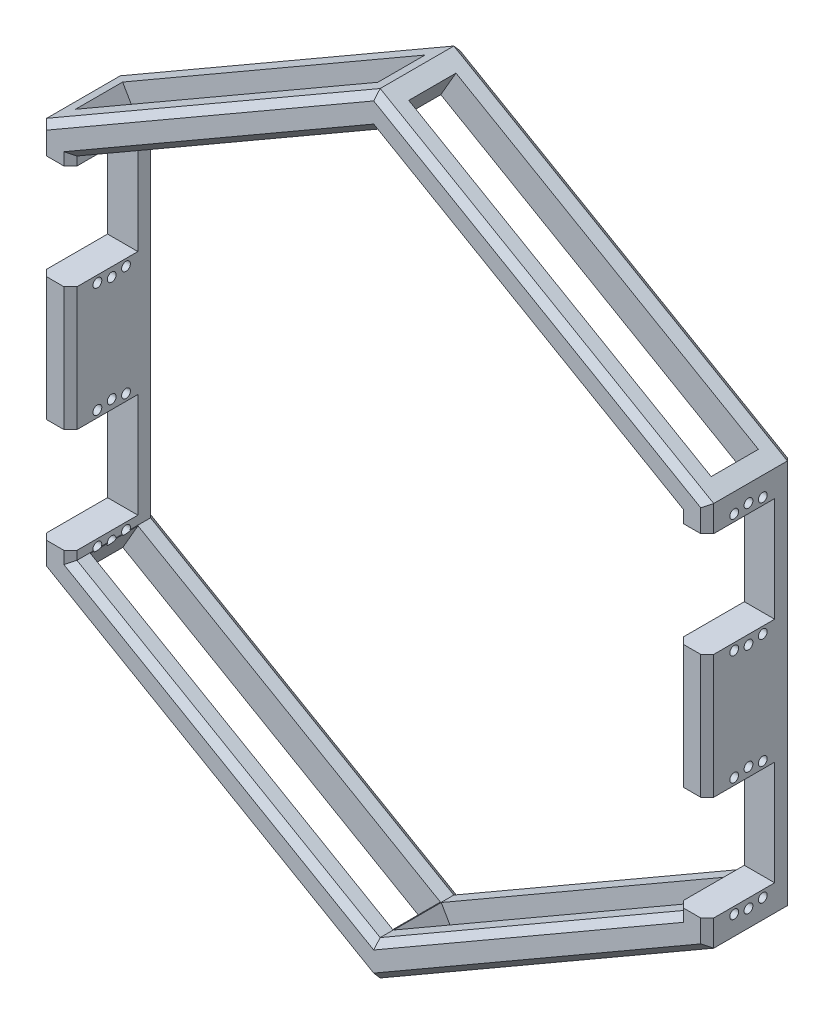
SolidWorks part; units mm, degrees
material "Caoutchouc"
ref_plane "Plan de face" through (0, 0, 0) normal (0, 0, 1) x (1, 0, 0)
ref_plane "Plan de dessus" through (0, 0, 0) normal (0, 1, 0) x (1, 0, 0)
ref_plane "Plan de droite" through (0, 0, 0) normal (1, 0, 0) x (0, 0, -1)
sketch "Esquisse1" plane through (0, 0, 0) normal (0, 0, 1) x (1, 0, 0)
  line L0 (-77, -44.456) -> (0, 0)
  line L1 (0, -8.0829) -> (70, -48.4974)
  line L2 (-77, -44.456) -> (-77, -133.3679)
  line L3 (70, -48.4974) -> (70, -129.3265)
  line L4 (77, -44.456) -> (77, -133.3679)
  line L5 (0, 0) -> (77, -44.456)
  line L6 (-77, -133.3679) -> (0, -177.8239)
  line L7 (0, -177.8239) -> (77, -133.3679)
  line L8 (70, -129.3265) -> (0, -169.741)
  line L9 (0, -169.741) -> (-70, -129.3265)
  line L10 (-70, -129.3265) -> (-70, -48.4974)
  line L11 (-70, -48.4974) -> (0, -8.0829)
  dimension "D1" = 120
  dimension "D2" = 120
  dimension "D3" = 7
  dimension "D4" = 7
  dimension "D5" = 7
  dimension "D6" = 70
extrude "Boss.-Extru.1" add sketch "Esquisse1" along normal blind 20
chamfer "Chanfrein1" distance 1.5 angle 45 24 edges at (-38.5, -155.5959, 20) (-77, -88.9119, 20) (-38.5, -22.228, 20) (38.5, -22.228, 20) (38.5, -155.5959, 20) (77, -88.9119, 20) (-77, -88.9119, 0) (-38.5, -155.5959, 0) (38.5, -155.5959, 0) (77, -88.9119, 0) (38.5, -22.228, 0) (-38.5, -22.228, 0) (-35, -149.5337, 20) (-70, -88.9119, 20) (-35, -28.2902, 20) (35, -28.2902, 20) (70, -88.9119, 20) (35, -149.5337, 20) (-35, -149.5337, 0) (35, -149.5337, 0) (70, -88.9119, 0) (35, -28.2902, 0) (-70, -88.9119, 0) (-35, -28.2902, 0)
sketch "Esquisse4" plane through (-70, 0, 0) normal (1, 0, 0) x (0, 0, -1)
  line L0 (-18.5, -48.4974) -> (-1.5, -48.4974) construction
  line L1 (-21.8389, -50.4974) -> (-4.435, -50.4974)
  line L2 (-21.8389, -50.4974) -> (-21.8389, -74.6274)
  line L3 (-21.8389, -74.6274) -> (-4.435, -74.6274)
  line L4 (-4.435, -50.4974) -> (-4.435, -74.6274)
  line L7 (-36.7449, -88.9119) -> (25.0579, -88.9119) construction
  line L8 (-18.5, -129.3265) -> (-1.5, -129.3265) construction
  line L9 (-21.8389, -127.3265) -> (-4.435, -127.3265)
  line L10 (-4.435, -127.3265) -> (-4.435, -103.1965)
  line L11 (-21.8389, -127.3265) -> (-21.8389, -103.1965)
  line L12 (-21.8389, -103.1965) -> (-4.435, -103.1965)
  dimension "D1" = 2
  dimension "D4" = 24.13
extrude "Enlèv. mat.-Extru.1" cut sketch "Esquisse4" against normal blind 10 and the other way through all
sketch "Esquisse6" plane through (-77, 0, 0) normal (-1, 0, 0) x (0, 0, 1)
  line L0 (32.243, -62.5529) -> (-9.9857, -62.5529) construction
  line L1 (16.319, -50.6784) -> (10.4996, -50.6784) construction
  line L2 (16.319, -74.4274) -> (4.635, -74.4274) construction
  line L3 (-15.4771, -88.9119) -> (37.6916, -88.9119) construction
  line L4 (18.5, -74.6274) -> (4.435, -74.6274) construction
  line L5 (4.435, -103.1965) -> (18.5, -103.1965) construction
  circle A0 centre (13.779, -48.9004) radius 1.016
  circle A1 centre (10.477, -48.3924) radius 1.016
  circle A2 centre (7.175, -48.9004) radius 1.016
  circle A3 centre (7.175, -76.2054) radius 1.016
  circle A4 centre (10.477, -76.7134) radius 1.016
  circle A5 centre (13.779, -76.2054) radius 1.016
  circle A6 centre (7.175, -128.9235) radius 1.016
  circle A7 centre (10.477, -129.4315) radius 1.016
  circle A8 centre (13.779, -128.9235) radius 1.016
  circle A9 centre (7.175, -101.6185) radius 1.016
  circle A10 centre (10.477, -101.1105) radius 1.016
  circle A11 centre (13.779, -101.6185) radius 1.016
  dimension "D1" = 2.032
extrude "Enlèv. mat.-Extru.2" cut sketch "Esquisse6" against normal blind 15
ref_plane "Plan1" through (0, 0, 0) normal (1, 0, 0) x (0, 0, -1)
mirror "Symétrie1" about plane through (0, 0, 0) normal (1, 0, 0) of "Enlèv. mat.-Extru.2"
sketch "Esquisse8" plane through (0, 0, 0) normal (-0.5, 0.866, 0) x (0, 0, 1)
  line L0 (18.5, -88.9119) -> (1.5, -88.9119) construction
  line L1 (4.55, -84.7619) -> (15.45, -84.7619)
  line L2 (4.55, -84.7619) -> (4.55, -4.15)
  line L3 (4.55, -4.15) -> (15.45, -4.15)
  line L4 (15.45, -84.7619) -> (15.45, -4.15)
  line L5 (18.5, -88.9119) -> (18.5, 0) construction
  line L6 (1.5, 0) -> (1.5, -88.9119) construction
  line L7 (18.5, 0) -> (1.5, 0) construction
  dimension "D1" = 4.15
  dimension "D2" = 3.05
  dimension "D3" = 3.05
  dimension "D4" = 4.15
extrude "Enlèv. mat.-Extru.3" cut sketch "Esquisse8" against normal up to surface (7 mm away) up to face at (-55.5935, -40.1798, 10.2862)
sketch "Esquisse9" plane through (0, 0, 0) normal (0.5, 0.866, 0) x (0, 0, -1)
  line L0 (-15.45, 2.075) -> (-4.55, 2.075) construction
  line L1 (-15.5, -84.7619) -> (-4.6, -84.7619)
  line L2 (-15.5, -84.7619) -> (-15.5, -4.15)
  line L3 (-15.5, -4.15) -> (-4.6, -4.15)
  line L4 (-4.6, -84.7619) -> (-4.6, -4.15)
  line L6 (-18.5, 0) -> (-1.5, 0) construction
  line L7 (-18.5, 0) -> (-18.5, -88.9119) construction
  line L8 (-18.5, -88.9119) -> (-1.5, -88.9119) construction
  dimension "D1" = 4.15
  dimension "D2" = 3
  dimension "D3" = 4.15
extrude "Enlèv. mat.-Extru.4" cut sketch "Esquisse9" against normal up to surface (7 mm away) up to face at (55.5935, -40.1798, 10.2862)
sketch "Esquisse10" plane through (-77, -133.3679, 0) normal (-0.5, -0.866, 0) x (0, 0, 1)
  line L0 (15.5, -4.15) -> (15.5, -84.7619) construction
  line L1 (4.5, -84.7619) -> (15.5, -84.7619)
  line L2 (4.5, -84.7619) -> (4.5, -4.15)
  line L3 (4.5, -4.15) -> (15.5, -4.15)
  line L4 (15.5, -84.7619) -> (15.5, -4.15)
  line L5 (15.5, -84.7619) -> (4.6, -84.7619) construction
  line L6 (18.5, -88.9119) -> (1.5, -88.9119) construction
  line L7 (1.5, 0) -> (1.5, -88.9119) construction
  line L8 (18.5, -88.9119) -> (18.5, 0) construction
  dimension "D1" = 4.15
  dimension "D2" = 3
  dimension "D3" = 3
sketch "Esquisse11" plane through (77, -133.3679, 0) normal (0.5, -0.866, 0) x (0, 0, -1)
  line L1 (-15.5, -4.15) -> (-4.5, -4.15)
  line L2 (-15.5, -4.15) -> (-15.5, -84.7619)
  line L3 (-15.5, -84.7619) -> (-4.5, -84.7619)
  line L4 (-4.5, -4.15) -> (-4.5, -84.7619)
  line L6 (-4.5, -90.9869) -> (-15.5, -90.9869) construction
  line L7 (-4.55, -4.15) -> (-4.55, -84.7619) construction
  line L8 (-18.5, 0) -> (-1.5, 0) construction
  line L9 (-1.5, -88.9119) -> (-1.5, 0) construction
  dimension "D1" = 4.15
  dimension "D2" = 3
extrude "Enlèv. mat.-Extru.5" cut sketch "Esquisse11" against normal up to surface (7 mm away) up to face at (55.5935, -137.6441, 10.2862)
extrude "Enlèv. mat.-Extru.6" cut sketch "Esquisse10" against normal up to surface (7 mm away) up to face at (-55.5935, -137.6441, 10.2862)
